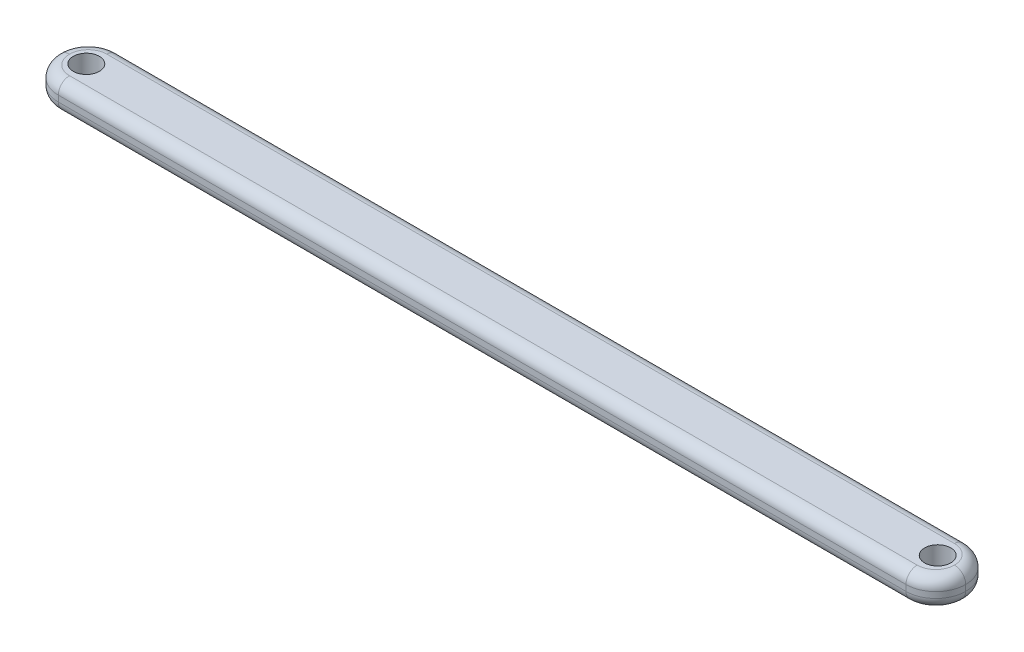
SolidWorks part; units mm, degrees
material "ABS"
ref_plane "Front Plane" through (0, 0, 0) normal (0, 0, 1) x (1, 0, 0)
ref_plane "Top Plane" through (0, 0, 0) normal (0, 1, 0) x (1, 0, 0)
ref_plane "Right Plane" through (0, 0, 0) normal (1, 0, 0) x (0, 0, -1)
sketch "Sketch1" plane through (0, 0, 0) normal (0, 1, 0) x (1, 0, 0)
  line L1 (-60.75, 4) -> (60.75, 4)
  line L2 (-60.75, 4) -> (-60.75, -4)
  line L3 (-60.75, -4) -> (60.75, -4)
  line L4 (60.75, 4) -> (60.75, -4)
  line L5 (-60.75, 4) -> (60.75, -4) construction
  line L6 (-60.75, -4) -> (60.75, 4) construction
  point P0 (0, 0)
  dimension "D1" = 8
  dimension "D2" = 121.5
extrude "Boss-Extrude1" add sketch "Sketch1" along normal blind 3.8
sketch "Sketch2" plane through (0, 3.8, 0) normal (0, 1, 0) x (1, 0, 0)
  line L0 (0, 0) -> (-57, 0) construction
  line L1 (0, 0) -> (57, 0) construction
  circle A0 centre (-57, 0) radius 1.75
  circle A1 centre (57, 0) radius 1.75
  dimension "D3" = 3.5
  dimension "D4" = 3.5
  dimension "D1" = 57
  dimension "D2" = 57
extrude "Cut-Extrude4" cut sketch "Sketch2" against normal through all
fillet "Fillet1" radius 4 4 edges at (60.75, 1.9, -4) (60.75, 1.9, 4) (-60.75, 1.9, 4) (-60.75, 1.9, -4)
fillet "Fillet2" radius 1.5 12 edges at (59.5784, 0, -2.8284) (59.5784, 0, 2.8284) (0, 0, 4) (-59.5784, 0, 2.8284) (-59.5784, 0, -2.8284) (59.5784, 3.8, -2.8284) (59.5784, 3.8, 2.8284) (0, 3.8, 4) (-59.5784, 3.8, 2.8284) (-59.5784, 3.8, -2.8284) (0, 0, -4) (0, 3.8, -4)
